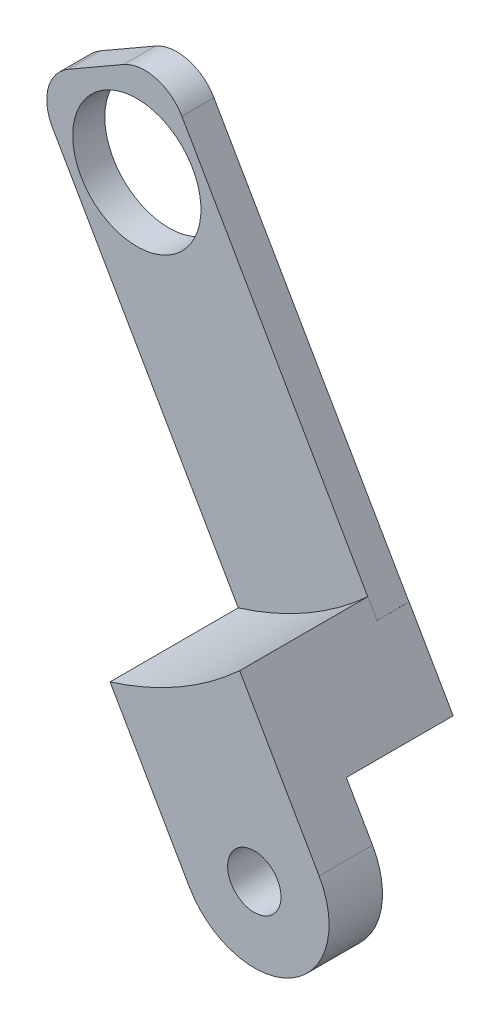
SolidWorks part; units mm, degrees
ref_plane "Ebene vorne" through (0, 0, 0) normal (0, 0, 1) x (1, 0, 0)
ref_plane "Ebene oben" through (0, 0, 0) normal (0, 1, 0) x (1, 0, 0)
ref_plane "Ebene rechts" through (0, 0, 0) normal (1, 0, 0) x (0, 0, -1)
sketch "Skizze1" plane through (0, 0, 0) normal (0, 0, 1) x (1, 0, 0)
  line L0 (-6.0683, -3.4893) -> (-13.5036, 9.4416)
  line L1 (0, 0) -> (-23, 40) construction
  line L2 (6.0683, 3.4893) -> (-1.3669, 16.4202)
  circle A0 centre (0, 0) radius 2.5
  circle A1 centre (0, 0) radius 7
  circle A2 centre (-23, 40) radius 32
  dimension "D1" = 5
  dimension "D2" = 14
  dimension "D3" = 64
  dimension "D4" = 23
  dimension "D5" = 40
extrude "Aufsatz-Linear austragen1" add sketch "Skizze1" along normal blind 5 contours L1 A1 L2 A2 | A1 L1 A2 L0 | A0 A1 region at (-6.5671, 1.7721, 0) region at (-8.2533, 6.5749, 0) region at (-1.5305, 10.4405, 0)
sketch "Skizze2" plane through (0, 0, 0) normal (0, 0, -1) x (-1, 0, 0)
  line L0 (13.5036, 9.4416) -> (1.3669, 16.4202)
  line L1 (6.0683, -3.4893) -> (13.5036, 9.4416) construction
  line L2 (1.3669, 16.4202) -> (-3.6178, 7.7511)
  line L3 (-6.0683, 3.4893) -> (1.3669, 16.4202) construction
  line L4 (-3.6178, 7.7511) -> (8.5189, 0.7725)
  line L5 (8.5189, 0.7725) -> (13.5036, 9.4416)
  circle A0 centre (23, 40) radius 32
  line M6 (6.0683, -3.4893) -> (13.5036, 9.4416)
  arc M7 (13.5036, 9.4416) -> (1.3669, 16.4202) centre (23, 40) cw
  line M8 (1.3669, 16.4202) -> (-6.0683, 3.4893)
  dimension "D1" = 10
extrude "Aufsatz-Linear austragen2" add sketch "Skizze2" along normal offset from surface (7 mm away) 1 contours L4 M8 M6 M7 region at (-4.8152, 8.3743, 0) offset beyond the face yes
sketch "Skizze3" plane through (0, 0, -7) normal (0, 0, -1) x (-1, 0, 0)
  line L0 (0.5236, 14.9119) -> (18.7739, 46.6517)
  line L1 (-3.6178, 7.7511) -> (1.3669, 16.4202) construction
  line L2 (12.6423, 7.9437) -> (30.8927, 39.6834)
  line L3 (24.2355, 48.1255) -> (29.4189, 45.145)
  circle A0 centre (21.8459, 39.8975) radius 32.8469
  circle A2 centre (22.9955, 39.9922) radius 6
  arc A3 (18.7739, 46.6517) -> (24.2355, 48.1255) centre (22.2416, 44.6578) cw
  arc A4 (30.8927, 39.6834) -> (29.4189, 45.145) centre (27.425, 41.6773) ccw
  point P8 (21.7063, 51.6992)
  point P11 (23, 40)
  line M7 (-3.6178, 7.7511) -> (8.5189, 0.7725)
  line M8 (8.5189, 0.7725) -> (13.5036, 9.4416)
  arc M9 (13.5036, 9.4416) -> (1.3669, 16.4202) centre (23, 40) cw
  line M10 (1.3669, 16.4202) -> (-3.6178, 7.7511)
  dimension "D1" = 4
  dimension "D2" = 12
extrude "Aufsatz-Linear austragen3" add sketch "Skizze3" along normal blind 3 contours L2 A4 L3 A3 L0 A2 M9 | L0 A0 L2 M9 | A0 M10 M7 M8 region at (-4.4931, 7.6936, -7) region at (-6.5338, 11.9792, -7) region at (-15.2844, 26.5556, -7)
